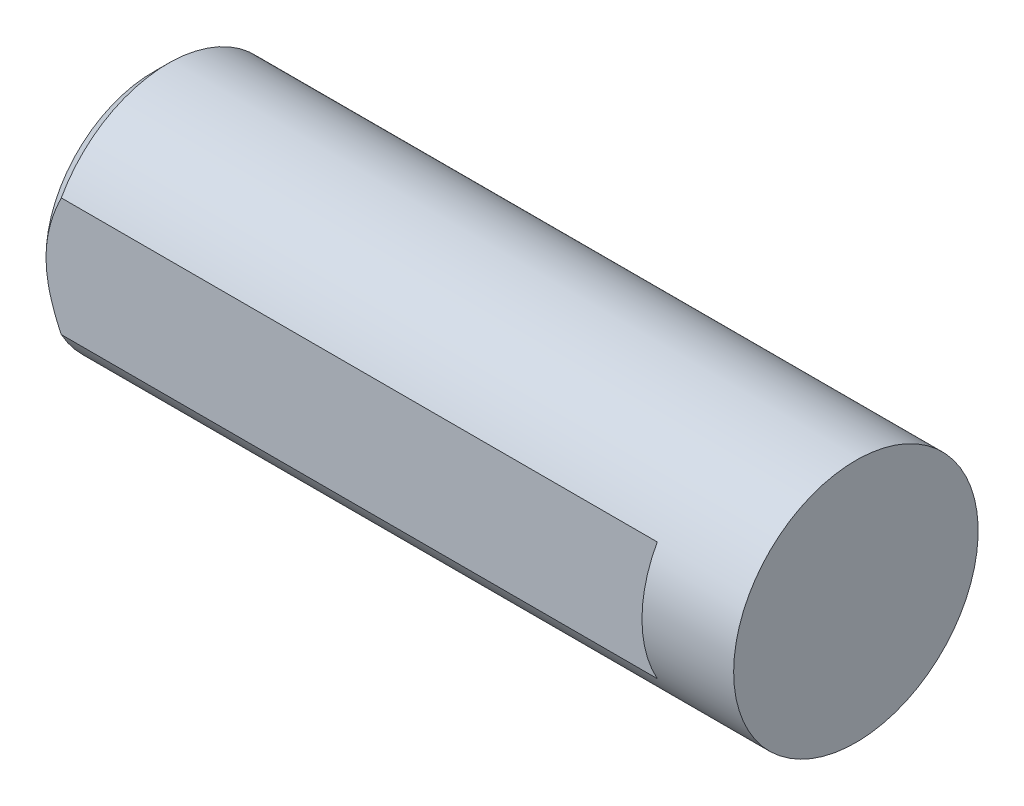
SolidWorks part; units mm, degrees
ref_plane "Plan de face" through (0, 0, 0) normal (0, 0, 1) x (1, 0, 0)
ref_plane "Plan de dessus" through (0, 0, 0) normal (0, 1, 0) x (1, 0, 0)
ref_plane "Plan de droite" through (0, 0, 0) normal (1, 0, 0) x (0, 0, -1)
sketch "Esquisse1" plane through (0, 0, 0) normal (0, 0, 1) x (1, 0, 0)
  line L0 (-20.5955, 0) -> (24.0427, 0) construction
  line L2 (0, 0) -> (23, 0)
  line L3 (0, 0) -> (0, 4)
  line L4 (0, 4) -> (23, 4)
  line L5 (23, 0) -> (23, 4)
  dimension "D1" = 23
  dimension "D2" = 8
revolve "Révolution1" add sketch "Esquisse1" angle 360 about L0
ref_plane "Plan1" through (0, 0, 4) normal (0, 0, 1) x (1, 0, 0)
sketch "Esquisse2" plane through (0, 0, 4) normal (0, 0, 1) x (1, 0, 0)
  line L0 (-7.5476, 0) -> (27.5248, 0) construction
  line L2 (0, 5) -> (20, 5)
  line L3 (0, 5) -> (0, -5)
  line L4 (0, -5) -> (20, -5)
  line L5 (20, 5) -> (20, -5)
  line L7 (0, 4) -> (0, -4) construction
  point P11 (-2.9929, -2.9504)
  dimension "D1" = 10
  dimension "D2" = 20
extrude "Enlèv. mat.-Extru.1" cut sketch "Esquisse2" against normal blind 0.5
chamfer "Chanfrein1" distance 0.5 angle 45 1 edges at (0, 0, -4)
